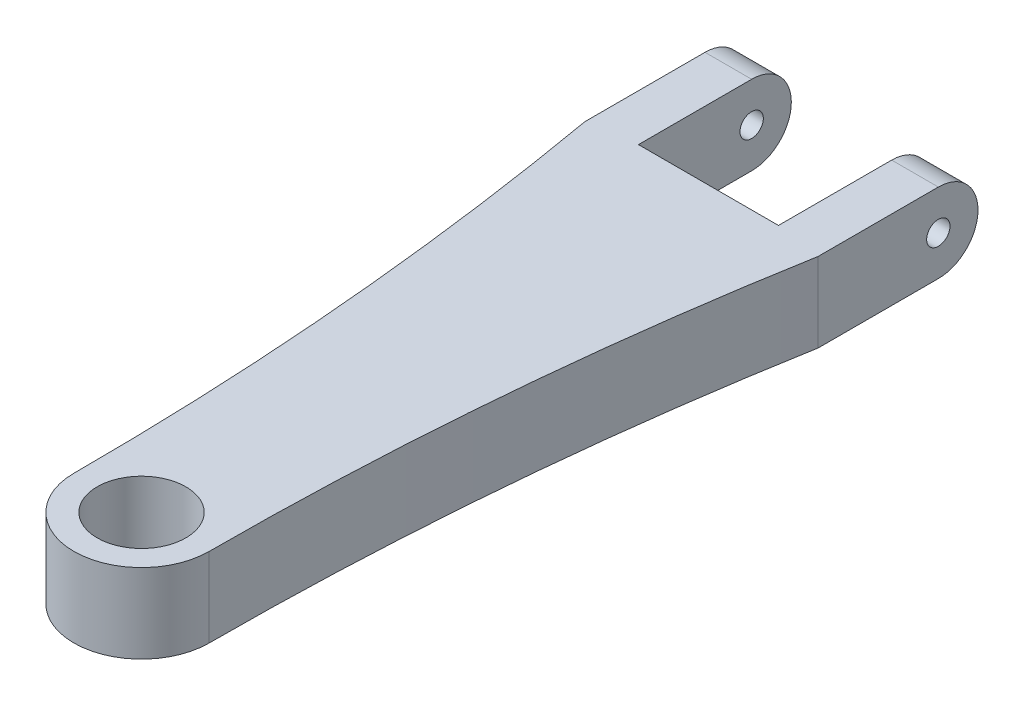
SolidWorks part; units mm, degrees
ref_plane "Front Plane" through (0, 0, 0) normal (0, 0, 1) x (1, 0, 0)
ref_plane "Top Plane" through (0, 0, 0) normal (0, 1, 0) x (1, 0, 0)
ref_plane "Right Plane" through (0, 0, 0) normal (1, 0, 0) x (0, 0, -1)
sketch "Sketch1" plane through (0, 0, 0) normal (0, 1, 0) x (1, 0, 0)
  line L0 (-31.75, 152.4) -> (31.75, 152.4)
  line L1 (0, 0) -> (0, 152.4) construction
  circle A0 centre (0, 0) radius 12.065
  circle A1 centre (0, 0) radius 152.4 construction
  arc A2 (-18.415, 0) -> (18.415, 0) centre (0, 0) ccw
  arc A3 (-31.75, 152.4) -> (-18.415, 0) centre (-895.9396, 0) cw
  arc A4 (31.75, 152.4) -> (18.415, 0) centre (895.9396, 0) ccw
  circle A6 centre (0, 0) radius 18.415 construction
  point P7 (0, 152.4)
  point P14 (18.0975, 0)
  dimension "D1" = 24.13
  dimension "D2" = 152.4
  dimension "D4" = 63.5
  dimension "D3" = 6.35
extrude "Boss-Extrude1" add sketch "Sketch1" along normal mid plane 21.59
sketch "Sketch3" [suppressed] plane through (0, 0, -152.4) normal (0, 0, -1) x (-1, 0, 0)
  line L0 (-1000, 0) -> (49000, 0) construction
  line L1 (0, -15.5111) -> (0, 15.5111) construction
  circle A0 centre (-25.4, 0) radius 3.175
  circle A1 centre (25.4, 0) radius 3.175
  point P6 (0, 0)
  dimension "D1" = 6.35
  dimension "D2" = 25.4
sketch "Sketch4" plane through (0, 0, -152.4) normal (0, 0, -1) x (-1, 0, 0)
  line L0 (0, -23.7718) -> (0, 23.7718) construction
  line L1 (48.961, 0) -> (-48.961, 0) construction
  line L2 (-19.05, 10.795) -> (-19.05, -10.795)
  line L3 (-31.75, 10.795) -> (31.75, 10.795) construction
  line L4 (-31.75, -10.795) -> (31.75, -10.795) construction
  line L6 (-31.75, 10.795) -> (-31.75, -10.795)
  line L7 (-31.75, 10.795) -> (-19.05, 10.795)
  line L8 (-31.75, -10.795) -> (-19.05, -10.795)
  line L9 (31.75, -10.795) -> (19.05, -10.795)
  line L10 (19.05, 10.795) -> (19.05, -10.795)
  line L11 (31.75, 10.795) -> (19.05, 10.795)
  line L12 (31.75, 10.795) -> (31.75, -10.795)
  point P4 (0, 0)
  point P8 (0, 0)
  point P20 (0, 0)
  point P21 (0, 0)
  line M3 (-31.75, -10.795) -> (31.75, -10.795)
  line M4 (31.75, -10.795) -> (31.75, 10.795)
  line M5 (31.75, 10.795) -> (-31.75, 10.795)
  line M6 (-31.75, 10.795) -> (-31.75, -10.795)
  dimension "D1" = 19.05
  dimension "D2" = 12.7
sketch "Sketch5" plane through (0, 0, -152.4) normal (0, 0, -1) x (-1, 0, 0)
  line L0 (-31.75, 10.795) -> (31.75, 10.795) construction
  line L1 (-19.05, -10.795) -> (19.05, -10.795)
  line L2 (-19.05, -10.795) -> (-19.05, 10.795)
  line L3 (-19.05, 10.795) -> (19.05, 10.795)
  line L4 (19.05, -10.795) -> (19.05, 10.795)
  line L5 (-19.05, -10.795) -> (19.05, 10.795) construction
  line L6 (-19.05, 10.795) -> (19.05, -10.795) construction
  line L7 (-31.75, 10.795) -> (-31.75, -10.795) construction
  point P0 (0, 0)
  dimension "D1" = 12.7
extrude "Boss-Extrude2" add sketch "Sketch5" along normal blind 101.6
sketch "Sketch6" plane through (19.05, 0, 0) normal (1, 0, 0) x (0, 0, -1)
  line L0 (152.4, -10.795) -> (154.2889, 10.795)
  line L1 (254, 10.795) -> (152.4, 10.795) construction
  line L2 (152.4, 10.795) -> (152.4, -10.795) construction
  line L3 (154.2889, 10.795) -> (254, 10.795)
  line L4 (254, 10.795) -> (254, -10.795)
  line L5 (254, -10.795) -> (152.4, -10.795)
  line L6 (153.3444, 0) -> (185.0944, 0) construction
  circle A0 centre (185.0944, 0) radius 3.175
  dimension "D3" = 6.35
  dimension "D1" = 5
  dimension "D2" = 31.75
extrude "Cut-Extrude1" cut sketch "Sketch6" against normal up to next
extrude "Boss-Extrude3" add sketch "Sketch4" along normal blind 50.8 contours L10 M5 M3 M4 | L2 M5 M6 M3 region at (25.4, 0, -152.4) region at (-25.4, 0, -152.4)
extrude "Cut-Extrude2" cut sketch "Sketch6<2>" against normal through all both and the other way through all contours A0
sketch "Sketch6<2>" plane through (19.05, 0, 0) normal (1, 0, 0) x (0, 0, -1) same geometry as "Sketch6"
sketch "Sketch7" plane through (31.75, 0, 0) normal (1, 0, 0) x (0, 0, -1)
  line L0 (185.0944, 10.795) -> (203.2, 10.795)
  line L1 (203.2, 10.795) -> (203.2, -10.795)
  line L2 (203.2, -10.795) -> (185.0944, -10.795)
  circle A0 centre (185.0944, 0) radius 10.795
  line M3 (152.4, -10.795) -> (203.2, -10.795)
  line M4 (203.2, -10.795) -> (203.2, 10.795)
  line M5 (203.2, 10.795) -> (152.4, 10.795)
extrude "Cut-Extrude3" cut sketch "Sketch7" against normal through all both and the other way through all contours A0 M3 M4 M5 region at (31.75, 0, -198.0849)
sketch "Sketch8" plane through (0, -10.795, 0) normal (0, -1, 0) x (1, 0, 0)
  line L14 (-22.7159, -144.78) -> (22.7159, -144.78)
  line L15 (-22.7159, -144.78) -> (22.7159, -144.78)
  arc A3 (-10.9192, -14.8285) -> (10.9192, -14.8285) centre (0, 0) ccw
  arc A6 (10.795, 0) -> (22.7159, -144.78) centre (895.9396, 0) ccw
  arc A7 (10.795, 0) -> (-10.795, 0) centre (0, 0) ccw
  arc A8 (-22.7159, -144.78) -> (-10.795, 0) centre (-895.9396, 0) ccw
  arc A9 (10.795, 0) -> (22.7159, -144.78) centre (895.9396, 0) ccw
  arc A10 (10.795, 0) -> (-10.795, 0) centre (0, 0) ccw
  arc A11 (-22.7159, -144.78) -> (-10.795, 0) centre (-895.9396, 0) ccw
  dimension "D1" = 7.62
extrude "Cut-Extrude4" [suppressed] cut sketch "Sketch8" against normal through all both and the other way through all contours A11 L15 A9 A3
